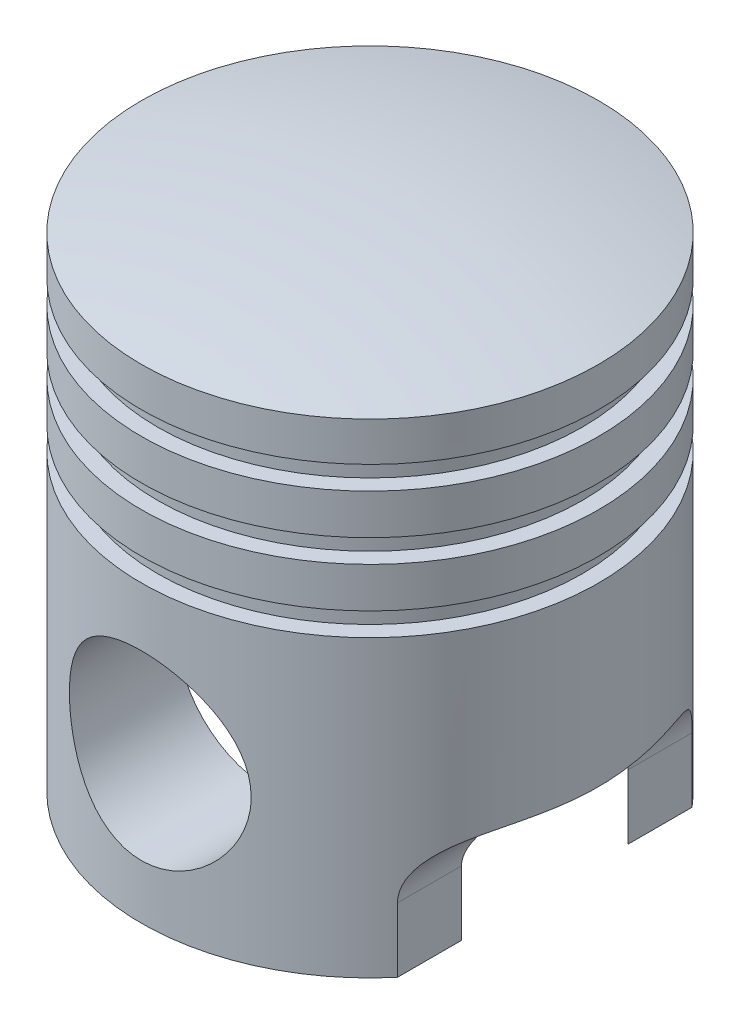
SolidWorks part; units mm, degrees
ref_plane "Front Plane" through (0, 0, 0) normal (0, 0, 1) x (1, 0, 0)
ref_plane "Top Plane" through (0, 0, 0) normal (0, 1, 0) x (1, 0, 0)
ref_plane "Right Plane" through (0, 0, 0) normal (1, 0, 0) x (0, 0, -1)
sketch "Sketch1" plane through (0, 0, 0) normal (0, 0, 1) x (1, 0, 0)
  line L0 (0, -52.5202) -> (0, 67.3071) construction
  line L1 (42.5, -48.6388) -> (42.5, 6.1612)
  line L2 (0, 46.3612) -> (0, 36.3612)
  line L3 (42.5, -48.6388) -> (36, -48.6388)
  line L4 (36, -48.6388) -> (36, -43.0388)
  line L8 (36, -0.062) -> (36, 34.3612)
  line L9 (34, 36.3612) -> (0, 36.3612)
  line L10 (42.5, 34.0612) -> (39.5, 34.0612)
  line L11 (39.5, 34.0612) -> (39.5, 29.7612)
  line L12 (39.5, 29.7612) -> (42.5, 29.7612)
  line L13 (42.5, 34.0612) -> (42.5, 41.3612)
  line L14 (42.5, 22.2612) -> (39.5, 22.2612)
  line L15 (39.5, 22.2612) -> (39.5, 17.9612)
  line L16 (39.5, 17.9612) -> (42.5, 17.9612)
  line L17 (42.5, 10.4612) -> (39.5, 10.4612)
  line L18 (39.5, 10.4612) -> (39.5, 6.1612)
  line L19 (39.5, 6.1612) -> (42.5, 6.1612)
  line L20 (42.5, 10.4612) -> (42.5, 17.9612)
  line L21 (42.5, 22.2612) -> (42.5, 29.7612)
  line L22 (25, -48.6388) -> (25, -43.0388) construction
  line L23 (36, -43.0388) -> (36, -0.062)
  arc A0 (36, 34.3612) -> (34, 36.3612) centre (34, 34.3612) ccw
  arc A2 (42.5, 41.3612) -> (0, 46.3612) centre (0, -136.7638) ccw
  arc A3 (19, -31.4394) -> (0, -26.6388) centre (0, -66.6388) ccw construction
  point P19 (41, 29.7612)
  point P22 (39.25, -48.6388)
  dimension "D6" = 2
  dimension "D8" = 40
  dimension "D1" = 90
  dimension "D2" = 36
  dimension "D3" = 54.8
  dimension "D4" = 42.5
  dimension "D5" = 36
  dimension "D9" = 4.3
  dimension "D10" = 3
  dimension "D12" = 85
  dimension "D13" = 22
  dimension "D14" = 25
  dimension "D11" = 3
revolve "Revolve1" add sketch "Sketch1" angle 360 about L0
sketch "Sketch3" plane through (0, 0, 0) normal (0, 0, 1) x (1, 0, 0)
  line L0 (0, -52.5202) -> (0, 67.3071) construction
  line L1 (-42.5, -48.6388) -> (42.5, -48.6388) construction
  circle A0 centre (0, -21.6388) radius 22.5
  dimension "D1" = 27
  dimension "D2" = 45
extrude "Boss-Extrude2" add sketch "Sketch3" along normal mid plane 72
sketch "Sketch2" plane through (0, 0, 0) normal (0, 0, 1) x (1, 0, 0)
  line L0 (-42.5, -48.6388) -> (42.5, -48.6388) construction
  line L1 (0, -55) -> (0, 55) construction
  line L2 (42.5, -48.6388) -> (42.5, -26.6388)
  line L3 (32.5, -48.6388) -> (42.5, -48.6388)
  line L4 (-32.5, -48.6388) -> (-32.5, -36.6388)
  line L5 (-32.5, -48.6388) -> (-42.5, -48.6388)
  line L6 (-42.5, -48.6388) -> (-42.5, -26.6388)
  line L7 (32.5, -48.6388) -> (32.5, -36.6388)
  circle A0 centre (0, -21.6388) radius 16.9
  arc A1 (-32.5, -36.6388) -> (-42.5, -26.6388) centre (-42.5, -36.6388) ccw
  arc A2 (32.5, -36.6388) -> (42.5, -26.6388) centre (42.5, -36.6388) cw
  dimension "D1" = 33.8
  dimension "D3" = 20
  dimension "D2" = 27
  dimension "D4" = 12
  dimension "D5" = 10
extrude "Cut-Extrude1" cut sketch "Sketch2" against normal mid plane 100
sketch "Sketch4" plane through (0, -48.6388, 0) normal (0, -1, 0) x (1, 0, 0)
  line L1 (-22.5, 19) -> (22.5, 19)
  line L2 (-22.5, 19) -> (-22.5, -19)
  line L3 (-22.5, -19) -> (22.5, -19)
  line L4 (22.5, 19) -> (22.5, -19)
  line L5 (-22.5, 19) -> (22.5, -19) construction
  line L6 (-22.5, -19) -> (22.5, 19) construction
  point P0 (0, 0)
  dimension "D1" = 38
  dimension "D2" = 45
extrude "Cut-Extrude2" cut sketch "Sketch4" against normal up to next
fillet "Fillet1" radius 2 2 edges at (-5.4855, 0.1823, 35.5796) (-5.4855, -43.4599, -35.5796)
